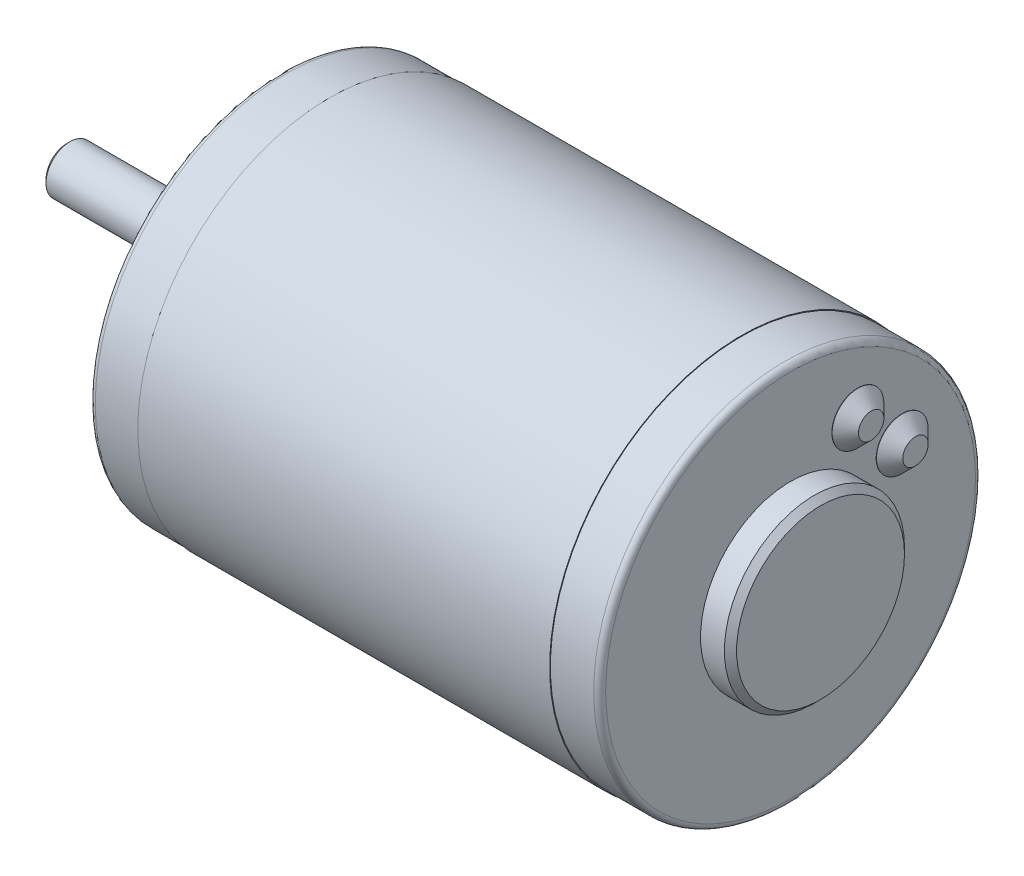
SolidWorks part; units mm, degrees
ref_plane "Front Plane" through (0, 0, 0) normal (0, 0, 1) x (1, 0, 0)
ref_plane "Top Plane" through (0, 0, 0) normal (0, 1, 0) x (1, 0, 0)
ref_plane "Right Plane" through (0, 0, 0) normal (1, 0, 0) x (0, 0, -1)
sketch "Sketch1" plane through (0, 0, 0) normal (0, 0, 1) x (1, 0, 0)
  line L0 (8.2296, 32.004) -> (8.2296, 0)
  line L1 (8.2296, 0) -> (76.9864, 0)
  line L2 (76.9864, 0) -> (76.9864, 32.004)
  line L3 (76.9864, 32.004) -> (8.2296, 32.004)
  line L4 (8.2296, 0) -> (76.9864, 0) construction
revolve "Revolve1" add sketch "Sketch1" angle 360 about L4 reverse direction yes
sketch "Sketch2" plane through (76.9864, 0, 0) normal (1, 0, 0) x (0, 0, -1)
  circle A0 centre (0, 0) radius 31.877
extrude "Boss-Extrude1" add sketch "Sketch2" along normal blind 8.2296
sketch "Sketch3" plane through (85.216, 0, 0) normal (1, 0, 0) x (0, 0, -1)
  circle A0 centre (0, 0) radius 15.0368
extrude "Boss-Extrude2" add sketch "Sketch3" along normal blind 5
sketch "Sketch4" plane through (8.2296, 0, 0) normal (-1, 0, 0) x (0, 0, 1)
  circle A0 centre (0, 0) radius 31.877
extrude "Boss-Extrude3" add sketch "Sketch4" along normal blind 8.2296
sketch "Sketch5" plane through (0, 0, 0) normal (-1, 0, 0) x (0, 0, 1)
  circle A0 centre (0, 0) radius 9.525
extrude "Boss-Extrude4" add sketch "Sketch5" along normal blind 4
sketch "Sketch6" plane through (-4, 0, 0) normal (-1, 0, 0) x (0, 0, 1)
  circle A0 centre (0, 0) radius 4
extrude "Boss-Extrude5" add sketch "Sketch6" along normal blind 31.6
ref_plane "Plane1" through (0, 2.8, 0) normal (0, -1, 0) x (1, 0, 0)
ref_plane "Plane2" through (0, 0, -18.6071) normal (0, 0, 1) x (1, 0, 0)
sketch "Sketch8" plane through (0, 0, -18.6071) normal (0, 0, 1) x (1, 0, 0)
  line L0 (85.216, 15.5254) -> (85.216, 11.2074)
  line L1 (85.216, 11.2074) -> (87.4639, 11.2074)
  line L2 (87.4639, 11.2074) -> (87.4639, 13.3254)
  line L3 (87.4639, 13.3254) -> (85.2639, 15.5254)
  line L4 (85.2639, 15.5254) -> (85.216, 15.5254)
  line L5 (85.216, 11.2074) -> (87.4639, 11.2074) construction
revolve "Revolve2" add sketch "Sketch8" angle 360 about L5 reverse direction yes
ref_plane "Plane3" through (0, 0, -11.2074) normal (0, 0, 1) x (1, 0, 0)
sketch "Sketch9" plane through (0, 0, -11.2074) normal (0, 0, 1) x (1, 0, 0)
  line L0 (85.216, 22.9251) -> (85.216, 18.6071)
  line L1 (85.216, 18.6071) -> (87.4639, 18.6071)
  line L2 (87.4639, 18.6071) -> (87.4639, 20.7251)
  line L3 (87.4639, 20.7251) -> (85.2639, 22.9251)
  line L4 (85.2639, 22.9251) -> (85.216, 22.9251)
  line L5 (85.216, 18.6071) -> (87.4639, 18.6071) construction
revolve "Revolve3" add sketch "Sketch9" angle 360 about L5 reverse direction yes
hole_wizard "#21 (0.159) Diameter Hole1" positions "Sketch11" profile "Sketch10" hole size "#21" standard "ANSI Inch"
sketch "Sketch11" plane through (0, 0, 0) normal (-1, 0, 0) x (0, 0, 1)
  point P0 (0, 25.4)
  point P1 (0, -25.4)
sketch "Sketch10" plane through (0, 25.4, 0) normal (0, 1, 0) x (0, 0, 1)
  line L0 (0, 0) -> (0, 14.8277)
  line L1 (0, 14.8277) -> (2.0193, 13.6144)
  line L2 (2.0193, 13.6144) -> (2.0193, 0)
  line L5 (2.0193, 0) -> (0, 0)
  line L10 (0, 14.8277) -> (-2.0193, 13.6144) construction
  line L11 (0, -6.35) -> (0, 107.95) construction
  dimension "Hole Dia." = 4.0386
  dimension "Hole Depth" = 13.6144
  dimension "Drill Angle" = 118
chamfer "Chamfer1" distance 1.016 angle 45 2 edges at (-4, 0, 9.525) (90.216, 0, -15.0368)
chamfer "Chamfer2" distance 0.5 angle 45 1 edges at (-35.6, 0, 4)
fillet "Fillet1" radius 1 2 edges at (0, 0, 31.877) (85.216, 0, -31.877) tangent propagation no
